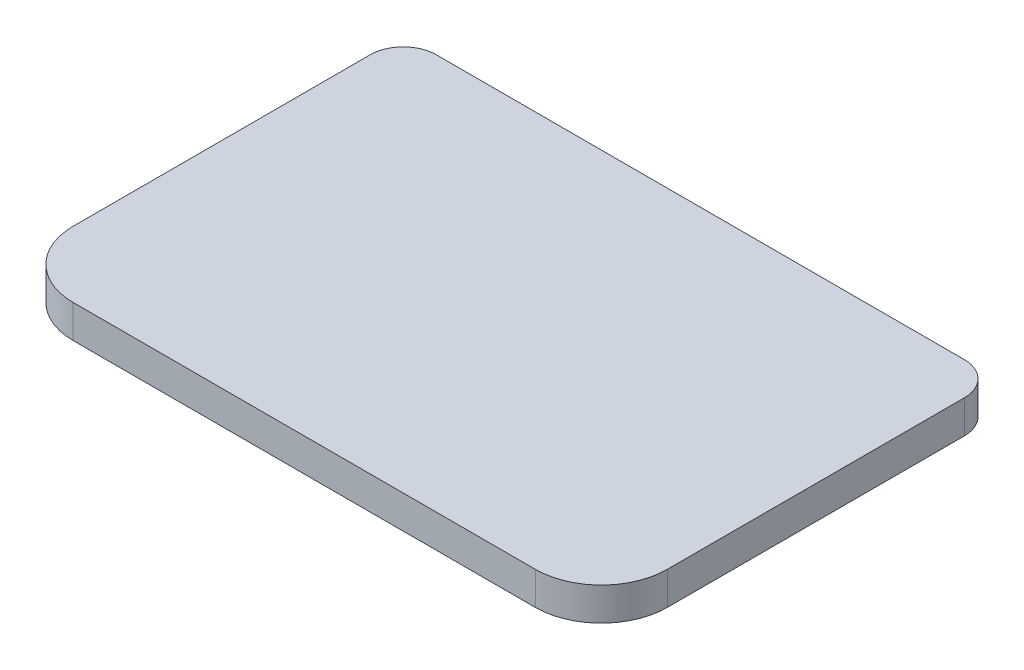
SolidWorks part; units mm, degrees
ref_plane "Front Plane" through (0, 0, 0) normal (0, 0, 1) x (1, 0, 0)
ref_plane "Top Plane" through (0, 0, 0) normal (0, 1, 0) x (1, 0, 0)
ref_plane "Right Plane" through (0, 0, 0) normal (1, 0, 0) x (0, 0, -1)
sketch "Sketch1" plane through (0, 0, 0) normal (0, 1, 0) x (1, 0, 0)
  line L1 (-28.575, 19.05) -> (28.575, 19.05)
  line L2 (-28.575, 19.05) -> (-28.575, -19.05)
  line L3 (-28.575, -19.05) -> (28.575, -19.05)
  line L4 (28.575, 19.05) -> (28.575, -19.05)
  line L5 (-28.575, 19.05) -> (28.575, -19.05) construction
  line L6 (-28.575, -19.05) -> (28.575, 19.05) construction
  point P0 (0, 0)
  dimension "D1" = 57.15
  dimension "D2" = 38.1
extrude "Boss-Extrude1" add sketch "Sketch1" along normal blind 3.175
fillet "Fillet1" radius 6.35 2 edges at (28.575, 1.5875, 19.05) (-28.575, 1.5875, 19.05)
fillet "Fillet2" radius 3.175 2 edges at (28.575, 1.5875, -19.05) (-28.575, 1.5875, -19.05)
